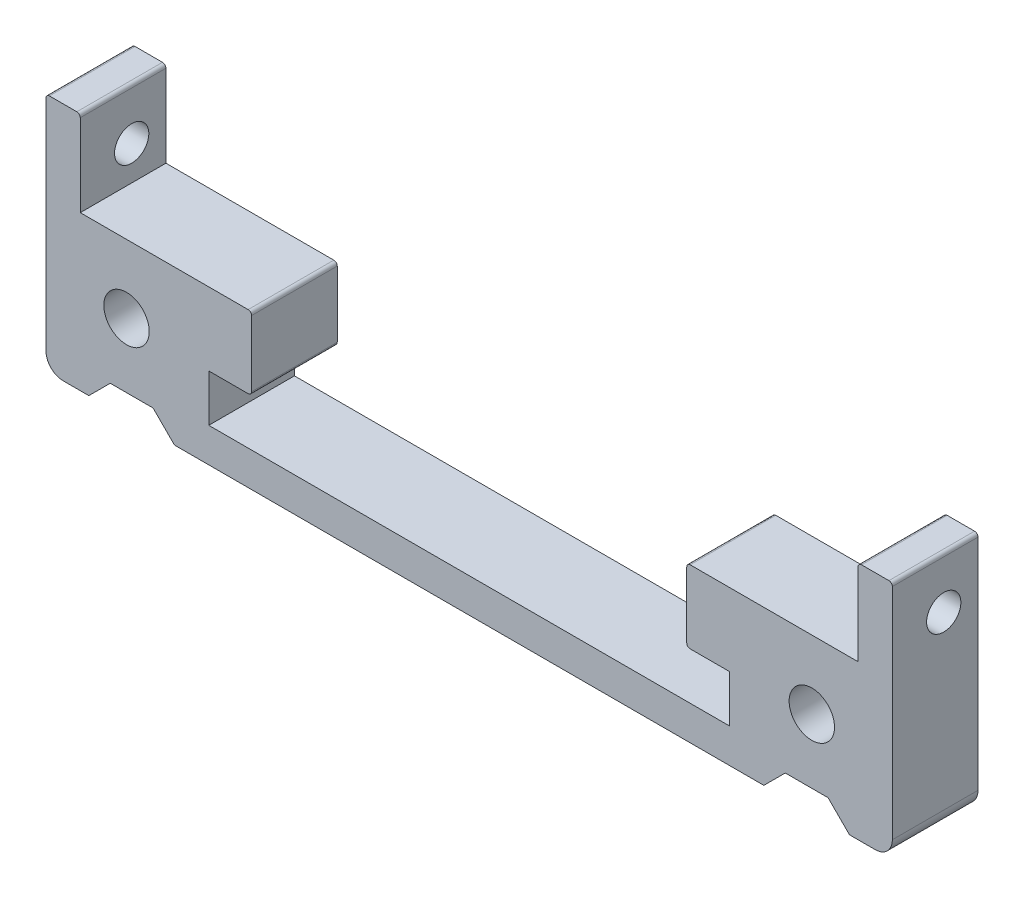
SolidWorks part; units mm, degrees
ref_plane "Front Plane" through (0, 0, 0) normal (0, 0, 1) x (1, 0, 0)
ref_plane "Top Plane" through (0, 0, 0) normal (0, 1, 0) x (1, 0, 0)
ref_plane "Right Plane" through (0, 0, 0) normal (1, 0, 0) x (0, 0, -1)
sketch "Sketch1" plane through (0, 0, 0) normal (0, 0, 1) x (1, 0, 0)
  line L0 (-49.4, 0) -> (0, 0) construction
  line L1 (0, 0) -> (0, 4)
  line L2 (0, 4) -> (-30.4, 4)
  line L3 (-30.4, 4) -> (-30.4, 9.5)
  line L4 (-30.4, 9.5) -> (-25.8, 9.5)
  line L5 (-25.4, 9.9) -> (-25.4, 17.6)
  line L6 (-25.8, 18) -> (-45.4, 18)
  line L7 (-45.4, 18) -> (-45.4, 27.6)
  line L8 (-45.8, 28) -> (-49, 28)
  line L9 (-49.4, 27.6) -> (-49.4, 2)
  line L10 (-47.4, 0) -> (-44.4, 0)
  line L11 (-44.4, 0) -> (-41.9, 2.5)
  line L12 (-41.9, 2.5) -> (-36.9, 2.5)
  line L13 (-36.9, 2.5) -> (-34.4, 0)
  line L14 (-34.4, 0) -> (0, 0)
  arc A0 (-49, 28) -> (-49.4, 27.6) centre (-49, 27.6) ccw
  arc A1 (-45.4, 27.6) -> (-45.8, 28) centre (-45.8, 27.6) ccw
  arc A2 (-25.8, 9.5) -> (-25.4, 9.9) centre (-25.8, 9.9) ccw
  arc A3 (-25.4, 17.6) -> (-25.8, 18) centre (-25.8, 17.6) ccw
  circle A4 centre (-40, 10) radius 2.65
  arc A5 (-47.4, 0) -> (-49.4, 2) centre (-47.4, 2) cw
  point P13 (-49.4, 28)
  point P16 (-45.4, 28)
  point P19 (-25.4, 9.5)
  point P22 (-25.4, 18)
  dimension "D9" = 0.4
  dimension "D10" = 5.3
  dimension "D16" = 2
  dimension "D1" = 4
  dimension "D2" = 4
  dimension "D3" = 10
  dimension "D4" = 20
  dimension "D5" = 5
  dimension "D6" = 14
  dimension "D7" = 5.5
  dimension "D8" = 45.4
  dimension "D11" = 40
  dimension "D12" = 10
  dimension "D13" = 5
  dimension "D14" = 5
  dimension "D15" = 5
extrude "Boss-Extrude1" add sketch "Sketch1" along normal blind 10
sketch "Sketch13" [suppressed] plane through (0, 0, 0) normal (0, 0, 1) x (1, 0, 0)
  line L0 (0, 4) -> (-30.4, 4)
  line L1 (-30.4, 4) -> (-30.4, 18)
  line L2 (-25.8, 18) -> (-45.4, 18) construction
  line L3 (-30.4, 18) -> (-49.4, 18)
  line L4 (-49.4, 32.6) -> (-49.4, 2) construction
  line L5 (-49.4, 18) -> (-49.4, 40)
  line L6 (-46.4, 43) -> (0, 43)
  line L7 (0, 43) -> (0, 4)
  arc A0 (-49.4, 40) -> (-46.4, 43) centre (-46.4, 40) cw
  circle A1 centre (-5, 38) radius 1.6
  circle A2 centre (-15, 38) radius 1.6
  circle A3 centre (-25, 38) radius 1.6
  circle A4 centre (-35, 38) radius 1.6
  circle A5 centre (-45, 38) radius 1.6
  circle A6 centre (-15, 30.5) radius 1.6
  circle A7 centre (-25, 30.5) radius 1.6
  circle A8 centre (-35, 30.5) radius 1.6
  circle A10 centre (-15, 23) radius 1.6
  circle A11 centre (-25, 23) radius 1.6
  circle A12 centre (-35, 23) radius 1.6
  circle A13 centre (-45, 23) radius 1.6 [skipped]
  circle A14 centre (-15, 15.5) radius 1.6
  circle A15 centre (-25, 15.5) radius 1.6 [skipped]
  circle A16 centre (-35, 15.5) radius 1.6 [skipped]
  circle A17 centre (-45, 15.5) radius 1.6 [skipped]
  circle A18 centre (-15, 8) radius 1.6
  circle A19 centre (-25, 8) radius 1.6 [skipped]
  circle A20 centre (-35, 8) radius 1.6 [skipped]
  circle A21 centre (-45, 8) radius 1.6 [skipped]
  circle A22 centre (-5, 30.5) radius 1.6
  circle A23 centre (-5, 23) radius 1.6
  circle A24 centre (-5, 15.5) radius 1.6
  circle A25 centre (-5, 8) radius 1.6
  circle A26 centre (-45, 30.5) radius 1.6 [skipped]
  dimension "D2" = 3
  dimension "D5" = 3.2
  dimension "D1" = 25
  dimension "D3" = 5
  dimension "D4" = 5
  dimension "D6" = 5
  dimension "D7" = 5
extrude "Boss-Extrude3" [suppressed] add sketch "Sketch13" along normal blind 2
sketch "Sketch10" plane through (-49.4, 0, 0) normal (-1, 0, 0) x (0, 0, 1)
  circle A0 centre (4, 22) radius 2
  dimension "D3" = 4
  dimension "D1" = 22
  dimension "D2" = 4
extrude "Cut-Extrude8" cut sketch "Sketch10" against normal up to next
sketch "Sketch2" [suppressed] plane through (0, 0, 0) normal (0, 0, 1) x (1, 0, 0)
  line L1 (0, 18) -> (0, 4)
  line L2 (0, 4) -> (-30.4, 4)
  line L3 (-30.4, 4) -> (-30.4, 18)
  line L4 (-25.8, 18) -> (-45.4, 18) construction
  line L7 (-30.4, 18) -> (0, 18)
extrude "Boss-Extrude2" [suppressed] add sketch "Sketch2" along normal up to surface (8 mm away) up to face at (-34.3604, 10.9711, 10)
sketch "Sketch7" [suppressed] plane through (0, 0, 0) normal (0, 0, 1) x (1, 0, 0)
  line L1 (-25.4, 16) -> (-28.4, 16)
  line L2 (-25.4, 16) -> (-25.4, 12.5)
  line L3 (-25.4, 12.5) -> (-28.4, 12.5)
  line L4 (-28.4, 16) -> (-28.4, 12.5)
  line L5 (-25.4, 10.9) -> (-25.4, 17.6) construction
  line L6 (-30.4, 10.5) -> (-25.8, 10.5) construction
  dimension "D1" = 3.5
  dimension "D2" = 2
  dimension "D3" = 3
extrude "Cut-Extrude4" [suppressed] cut sketch "Sketch7" along normal through all
sketch "Sketch8" [suppressed] plane through (0, 0, 0) normal (1, 0, 0) x (0, 0, -1)
  line L0 (-20, 4) -> (-20, 20.8836)
  line L1 (-20, 18) -> (-20, 27.6) construction
  line L2 (-20, 20.8836) -> (0, 20.8836)
  line L3 (0, 27.6) -> (0, 0) construction
  line L5 (-20, 4) -> (-15.5065, 14.3831)
  line L7 (0, 20.8836) -> (0, 18)
  line L8 (0, 18) -> (-10, 18)
  line L9 (-20, 18) -> (0, 18) construction
  arc A0 (-15.5065, 14.3831) -> (-10, 18) centre (-10, 12) cw
  dimension "D1" = 6
  dimension "D2" = 10
extrude "Cut-Extrude5" [suppressed] cut sketch "Sketch8" against normal blind 45.4
sketch "Sketch9" [suppressed] plane through (0, 0, 0) normal (0, 0, 1) x (1, 0, 0)
  circle A0 centre (-40, 10) radius 3.25
  dimension "D1" = 6.5
extrude "Cut-Extrude7" [suppressed] cut sketch "Sketch9" against normal blind 12 from offset 20
mirror "Mirror1" about plane through (0, 0, 0) normal (1, 0, 0) of "Cut-Extrude8", "Boss-Extrude1"
mirror "Mirror2" [suppressed] about plane through (0, 0, 0) normal (1, 0, 0)
mirror "Mirror3" [suppressed] about plane through (0, 0, 0) normal (1, 0, 0)
mirror "Mirror4" [suppressed] about plane through (0, 0, 0) normal (1, 0, 0)
fillet "Fillet1" [suppressed] radius 1
sketch "Sketch3" [suppressed] plane through (0, 0, 0) normal (0, 0, 1) x (1, 0, 0)
  line L0 (-17.9, 14.5) -> (-17.9, 6.5) construction
  line L1 (-15.9, 14.5) -> (-15.9, 6.5)
  line L2 (-19.9, 14.5) -> (-19.9, 6.5)
  line L3 (-45.4, 18) -> (-45.4, 32.6) construction
  line L4 (0, 4) -> (-30.4, 4) construction
  arc A0 (-15.9, 14.5) -> (-19.9, 14.5) centre (-17.9, 14.5) ccw
  arc A1 (-19.9, 6.5) -> (-15.9, 6.5) centre (-17.9, 6.5) ccw
  point P2 (-17.9, 10.5)
  dimension "D1" = 2
  dimension "D2" = 27.5
  dimension "D3" = 6
  dimension "D4" = 6.5
extrude "Cut-Extrude1" [suppressed] cut sketch "Sketch3" along normal through all
pattern_linear "LPattern1" [suppressed] count 6 spacing 6.75 along (1, 0, 0) of bodies 105
sketch "Sketch5" [suppressed] plane through (0, 0, 0) normal (0, 0, 1) x (1, 0, 0)
  line L1 (-25.8, 18) -> (-22.3, 18)
  line L2 (-25.8, 18) -> (-25.8, 10)
  line L3 (-25.8, 10) -> (-22.3, 10)
  line L4 (-22.3, 18) -> (-22.3, 10)
  dimension "D1" = 3.5
  dimension "D2" = 8
extrude "Cut-Extrude2" [suppressed] cut sketch "Sketch5" along normal through all
sketch "Sketch6" [suppressed] plane through (0, 0, 8) normal (0, 0, 1) x (1, 0, 0)
  circle A0 centre (-40, 10) radius 6
  circle A1 centre (40, 10) radius 6
  dimension "D1" = 12
extrude "Cut-Extrude3" [suppressed] cut sketch "Sketch6" along normal blind 4 from surface starting at face at (0, 12.0266, 0)
sketch "Sketch11" [suppressed] plane through (0, 0, 0) normal (0, 0, -1) x (-1, 0, 0)
  circle A0 centre (-25, 10) radius 1.6
  circle A1 centre (25.1086, 10) radius 1.6
  dimension "D3" = 3.2
  dimension "D1" = 10
  dimension "D2" = 25
extrude "Cut-Extrude9" [suppressed] cut sketch "Sketch11" against normal through all
sketch "Sketch12" [suppressed] plane through (0, 0, 0) normal (0, 0, -1) x (-1, 0, 0)
  circle A0 centre (-25, 10) radius 2
  circle A1 centre (25.1086, 10) radius 2
  dimension "D1" = 4
extrude "Cut-Extrude10" [suppressed] cut sketch "Sketch12" against normal blind 4
sketch "Sketch14" [suppressed] plane through (0, 0, 8) normal (0, 0, 1) x (1, 0, 0)
  line L0 (-45.4, 18) -> (45.4, 18) construction
  line L1 (-22.1086, 18) -> (22, 18)
  line L2 (-22.1086, 18) -> (-22.1086, 3)
  line L3 (-22.1086, 3) -> (22, 3)
  line L4 (22, 18) -> (22, 3)
  dimension "D1" = 3
  dimension "D2" = 15
  dimension "D3" = 3
extrude "Cut-Extrude11" [suppressed] cut sketch "Sketch14" against normal through all
fillet "Fillet3" [suppressed] radius 2
chamfer "Chamfer3" [suppressed] distance 1 angle 45
sketch "Sketch15" [suppressed] plane through (0, 0, 0) normal (1, 0, 0) x (0, 0, -1)
  line L0 (-8, 33) -> (-3, 33)
  line L1 (-8, 33) -> (-2, 33) construction
  line L2 (-3, 33) -> (-8, 28)
  line L3 (-8, 32.6) -> (-8, 2) construction
  line L4 (-8, 28) -> (-8, 33)
  dimension "D1" = 5
  dimension "D2" = 5
extrude "Cut-Extrude12" [suppressed] cut sketch "Sketch15" against normal through all both and the other way through all
fillet "Fillet4" [suppressed] radius 0.4
